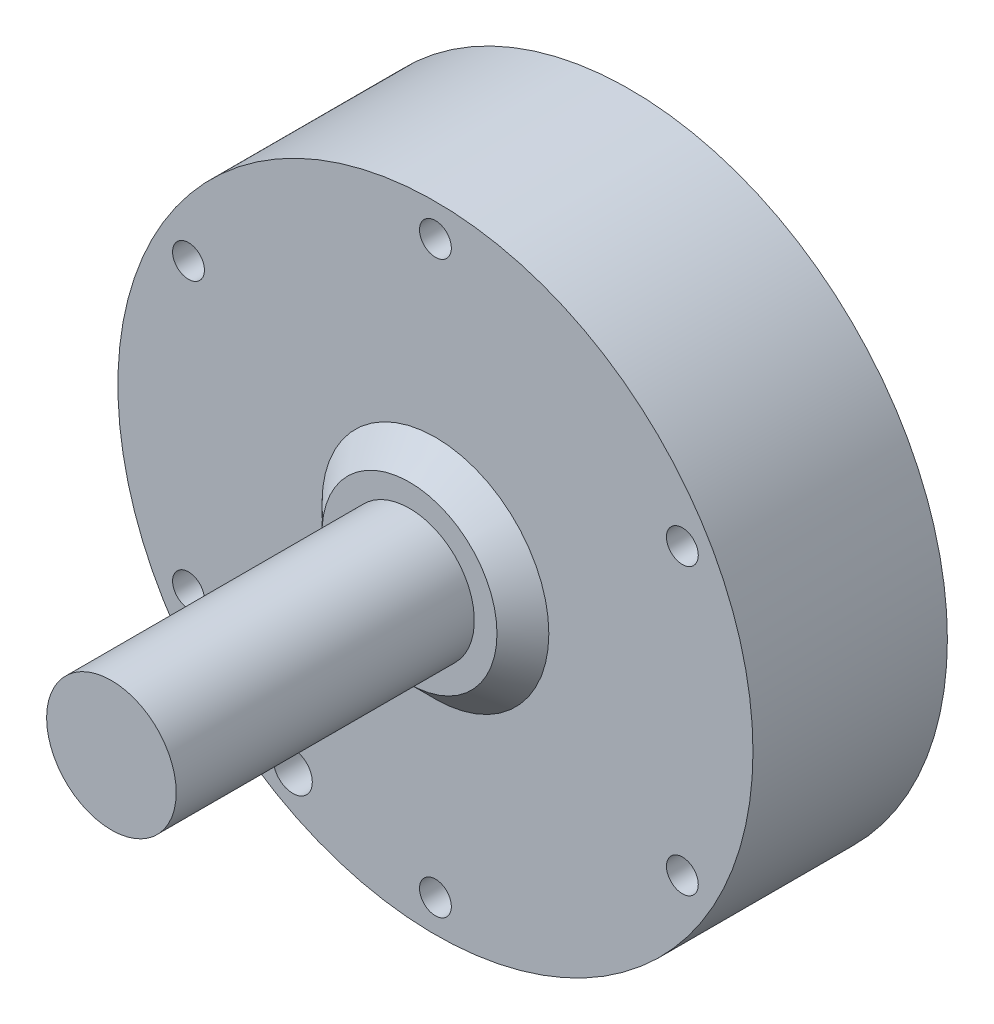
SolidWorks part; units mm, degrees
note: '?' marks a value the reader was unsure of.
ref_plane "Plane1" through (0, 0, 0) normal (0, 0, 1) x (1, 0, 0)
ref_plane "Plane2" through (0, 0, 0) normal (0, 1, 0) x (1, 0, 0)
ref_plane "Plane3" through (0, 0, 0) normal (1, 0, 0) x (0, 0, -1)
sketch "Esquisse1" plane through (0, 0, 0) normal (0, 0, 1) x (1, 0, 0)
  circle A0 centre (0, 0) radius 49
  dimension "D1" = 98
extrude "Base-Extrusion" add sketch "Esquisse1" along normal blind 30
sketch "Esquisse2" plane through (0, 0, 0) normal (1, 0, 0) x (0, 0, -1)
  line L0 (-30, 0) -> (-30, 17.5)
  line L1 (-30, 0) -> (0, 0) construction
  line L2 (-30, 17.5) -> (-34, 13.5)
  line L3 (-34, 13.5) -> (-34, 0)
  line L4 (-34, 0) -> (-30, 0)
  line L5 (-30, 49) -> (-30, -49) construction
  line L6 (-38.8589, 0) -> (34.2943, 0) construction
  dimension "D1" = 4
  dimension "D2" = 45
  dimension "D3" = 17.5
revolve "Boss.-Révol.1" add sketch "Esquisse2" angle 360 about L6
ref_plane "Plan5" through (-49, 0, 15) normal (-1, 0, 0) x (0, 1, 0)
sketch "Esquisse20" plane through (-49, 0, 15) normal (-1, 0, 0) x (0, 1, 0)
  line L1 (-13.5, -19) -> (13.5, -19) construction
  circle A0 centre (0, -3) radius 3
  dimension "D1" = 6
  dimension "D2" = 16
extrude "Enlèv. mat.-Extru.4" cut sketch "Esquisse20" against normal blind 12
sketch "Esquisse3" plane through (0, 0, 34) normal (0, 0, 1) x (1, 0, 0)
  circle A0 centre (0, 0) radius 10
  dimension "D1" = 20
extrude "Boss.-Extru.1" add sketch "Esquisse3" along normal blind 46
sketch "Esquisse11" plane through (0, 0, 30) normal (0, 0, 1) x (1, 0, 0)
  line L0 (0, 0) -> (0, -49) construction
  line L2 (0, 0) -> (-22, -38.1051) construction
  circle A0 centre (-22, -38.1051) radius 3
  circle A1 centre (0, 0) radius 49 construction
  dimension "D3" = 6
  dimension "D1" = 30
  dimension "D2" = 44
extrude "Enlèv. mat.-Extru.3" cut sketch "Esquisse11" against normal through all
hole_wizard "Perçage2" positions "Esquisse13" profile "Esquisse12" legacy
sketch "Esquisse13" plane through (0, 0, 30) normal (0, 0, 1) x (1, 0, 0)
  line L0 (0, -44) -> (0, 0) construction
  line L1 (-22, -38.1051) -> (0, 0) construction
  point P0 (0, -44)
  dimension "D1" = 30
  dimension "D2" = 44
sketch "Esquisse12" plane through (0, -44, 30) normal (1, 0, 0) x (0, -1, 0)
  line L0 (0, 0) -> (0, 26.4751)
  line L1 (0, 26.4751) -> (2.455, 25)
  line L2 (2.455, 25) -> (2.455, 0)
  line L4 (2.455, 0) -> (0, 0)
  line L6 (0, 26.4751) -> (-2.455, 25) construction
  line L7 (0, -4.2442) -> (0, 117.3081) construction
  dimension "Diamètre" = 4.91
  dimension "Profondeur" = 25
  dimension "Angle" = 118
cosmetic thread "Représentation de filetage1" parameters "D1"=15, "D2"=6
pattern_circular "Répétition circulaire1" count 6 over 360 about axis through (0, 0, 0) along (0, 0, 1) of "Perçage2"
ref_axis "Axe1" through (0, 0, 80) along (0, 0, -1)?
hole_wizard "Perçage4" positions "Esquisse17" profile "Esquisse16" hole size "M1.6" standard "Ansi Métrique"
sketch "Esquisse17" plane through (0, 0, 0) normal (0, 0, -1) x (-1, 0, 0)
  line L0 (0, 0) -> (21.242, 21.1844) construction
  line L1 (0, 0) -> (21.7629, -37.8131) construction
  point P0 (21.242, 21.1844)
  dimension "D1" = 105
  dimension "D2" = 30
sketch "Esquisse16" plane through (-21.242, 21.1844, 0) normal (1, 0, 0) x (0, 1, 0)
  line L0 (0, 0) -> (0, 21.8026)
  line L1 (0, 21.8026) -> (3, 20)
  line L2 (3, 20) -> (3, 0)
  line L5 (3, 0) -> (0, 0)
  line L10 (0, 21.8026) -> (-3, 20) construction
  line L11 (0, -6.35) -> (0, 107.95) construction
  dimension "Diamètre du perçage" = 6
  dimension "Profondeur du perçage" = 20
  dimension "Angle de pointe" = 118
pattern_circular "Répétition circulaire3" count 2 every 135 of "Perçage4"
hole_wizard "Perçage5" positions "Esquisse19" profile "Esquisse18" tap size "M6x1.0" standard "Ansi Métrique"
sketch "Esquisse19" plane through (0, 0, 0) normal (0, 0, -1) x (-1, 0, 0)
  line L0 (0, 0) -> (30, -0.0508) construction
  point P0 (30, -0.0508)
  dimension "D1" = 30
sketch "Esquisse18" plane through (-30, -0.0508, 0) normal (1, 0, 0) x (0, 1, 0)
  line L0 (0, 0) -> (0, 21.5022)
  line L1 (0, 21.5022) -> (2.5, 20)
  line L2 (2.5, 20) -> (2.5, 0)
  line L5 (2.5, 0) -> (0, 0)
  line L10 (0, 21.5022) -> (-2.5, 20) construction
  line L11 (0, -6.35) -> (0, 107.95) construction
  dimension "Diamètre du perçage" = 5
  dimension "Profondeur du perçage" = 20
  dimension "Angle de pointe" = 118
cosmetic thread "Représentation de filetage2" parameters "D1"=12, "D2"=6
pattern_circular "Répétition circulaire4" count 3 every 120 about axis through (0, 0, 0) along (0, 0, 1) of "Perçage5"
